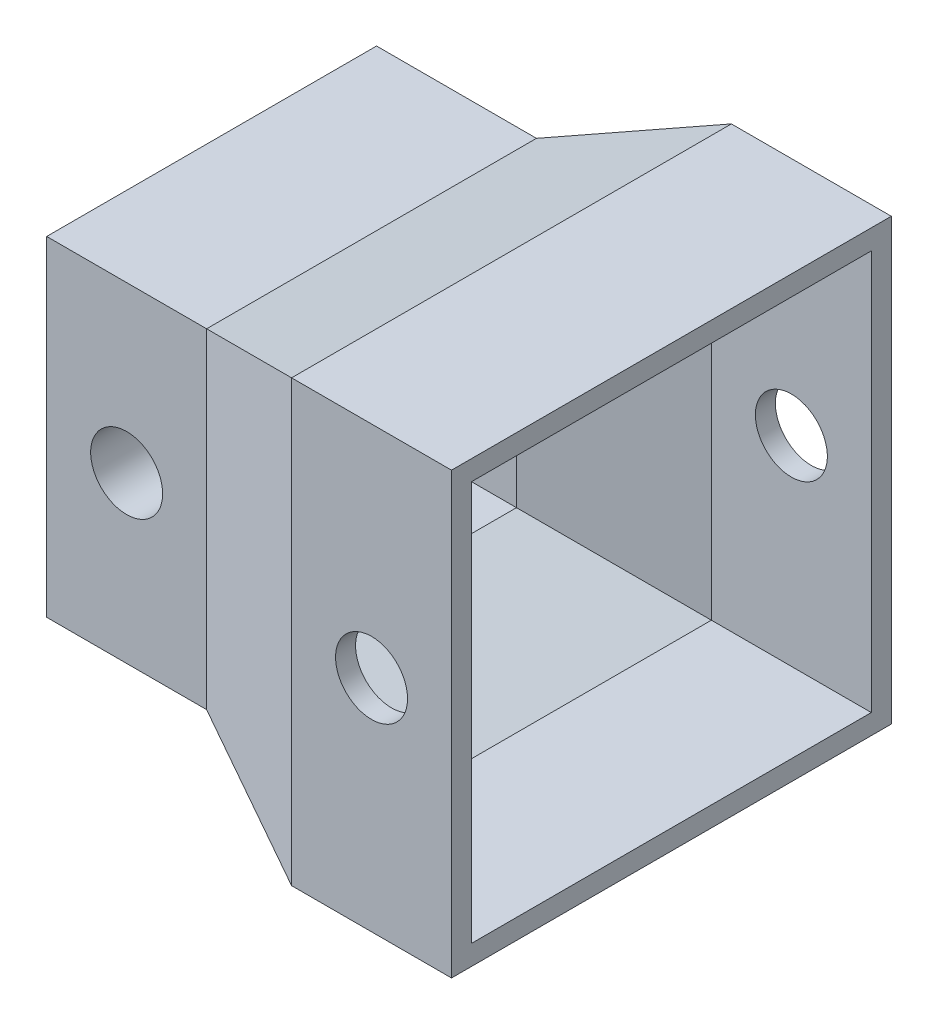
SolidWorks part; units mm, degrees
ref_plane "正面" through (0, 0, 0) normal (0, 0, 1) x (1, 0, 0)
ref_plane "平面" through (0, 0, 0) normal (0, 1, 0) x (1, 0, 0)
ref_plane "右側面" through (0, 0, 0) normal (1, 0, 0) x (0, 0, -1)
sketch "ｽｹｯﾁ1" plane through (0, 0, 0) normal (0, 0, 1) x (1, 0, 0)
  circle A0 centre (0, 0) radius 2.5
  dimension "D1" = 5
extrude "ﾎﾞｽ - 押し出し1" add sketch "ｽｹｯﾁ1" along normal blind 1.5
sketch "ｽｹｯﾁ2" plane through (0, 0, 1.5) normal (0, 0, 1) x (1, 0, 0)
  circle A0 centre (0, 0) radius 3.5
  dimension "D1" = 7
extrude "ﾎﾞｽ - 押し出し2" add sketch "ｽｹｯﾁ2" along normal blind 1
sketch "ｽｹｯﾁ3" plane through (0, 0, 2.5) normal (0, 0, 1) x (1, 0, 0)
  circle A0 centre (0, 0) radius 2.5 construction
  circle A1 centre (0, 0) radius 2.5
extrude "ﾎﾞｽ - 押し出し3" add sketch "ｽｹｯﾁ3" along normal blind 2.5
sketch "ｽｹｯﾁ4" plane through (0, 0, 5) normal (0, 0, 1) x (1, 0, 0)
  circle A1 centre (0, 0) radius 3.5
  circle A2 centre (0, 0) radius 3.5
  dimension "D1" = 0
extrude "ﾎﾞｽ - 押し出し4" add sketch "ｽｹｯﾁ4" along normal blind 1
sketch "ｽｹｯﾁ5" plane through (0, 0, 6) normal (0, 0, 1) x (1, 0, 0)
  circle A0 centre (0, 0) radius 2.5 construction
  circle A1 centre (0, 0) radius 2.5
extrude "ﾎﾞｽ - 押し出し5" add sketch "ｽｹｯﾁ5" along normal blind 2.5
sketch "ｽｹｯﾁ6" plane through (0, 0, 8.5) normal (0, 0, 1) x (1, 0, 0)
  circle A1 centre (0, 0) radius 3.5
  circle A2 centre (0, 0) radius 3.5
  dimension "D1" = 0
extrude "ﾎﾞｽ - 押し出し6" add sketch "ｽｹｯﾁ6" along normal blind 1
sketch "ｽｹｯﾁ7" plane through (0, 0, 9.5) normal (0, 0, 1) x (1, 0, 0)
  circle A0 centre (0, 0) radius 2.5 construction
  circle A1 centre (0, 0) radius 2.5
extrude "ﾎﾞｽ - 押し出し7" add sketch "ｽｹｯﾁ7" along normal blind 2.5
sketch "ｽｹｯﾁ10" plane through (0, 0, 12) normal (0, 0, 1) x (1, 0, 0)
  circle A1 centre (0, 0) radius 3.5
  circle A2 centre (0, 0) radius 3.5
  dimension "D1" = 0
extrude "ﾎﾞｽ - 押し出し9" add sketch "ｽｹｯﾁ10" along normal blind 1
sketch "ｽｹｯﾁ11" plane through (0, 0, 13) normal (0, 0, 1) x (1, 0, 0)
  circle A0 centre (0, 0) radius 2.5 construction
  circle A1 centre (0, 0) radius 2.5
extrude "ﾎﾞｽ - 押し出し10" add sketch "ｽｹｯﾁ11" along normal blind 1.5
sketch "ｽｹｯﾁ12" plane through (0, 0, 14.5) normal (0, 0, 1) x (1, 0, 0)
  circle A0 centre (0, 0) radius 1.8
  dimension "D1" = 3.6
extrude "ｶｯﾄ - 押し出し2" cut sketch "ｽｹｯﾁ12" against normal through all
ref_plane "平面1" through (15, 0, 0) normal (1, 0, 0) x (0, 0, -1)
sketch "ｽｹｯﾁ13" plane through (15, 0, 0) normal (1, 0, 0) x (0, 0, -1)
  line L0 (0, 0) -> (-7.25, 0) construction
  line L1 (-18.25, -11) -> (3.75, -11)
  line L2 (-18.25, -11) -> (-18.25, 11)
  line L3 (-18.25, 11) -> (3.75, 11)
  line L4 (3.75, -11) -> (3.75, 11)
  line L5 (-18.25, -11) -> (3.75, 11) construction
  line L6 (-18.25, 11) -> (3.75, -11) construction
  line L7 (-7.25, 0) -> (-14.5, 0) construction
  line L8 (-14.5, 2.5) -> (-14.5, -2.5) construction
  line L10 (2.75, -10) -> (-17.25, -10)
  line L11 (2.75, -10) -> (2.75, 10)
  line L12 (2.75, 10) -> (-17.25, 10)
  line L13 (-17.25, -10) -> (-17.25, 10)
  line L14 (2.75, -10) -> (-17.25, 10) construction
  line L15 (2.75, 10) -> (-17.25, -10) construction
  point P4 (-7.25, 0)
  dimension "D1" = 22
  dimension "D2" = 22
  dimension "D3" = 1
extrude "ﾎﾞｽ - 押し出し11" add sketch "ｽｹｯﾁ13" along normal blind 4 and the other way blind 4 separate body
sketch "ｽｹｯﾁ14" plane through (0, 0, 0) normal (1, 0, 0) x (0, 0, -1)
  line L0 (-18.25, 11) -> (3.75, -11) construction
  line L1 (1, -8.25) -> (-15.5, -8.25)
  line L2 (1, -8.25) -> (1, 8.25)
  line L3 (1, 8.25) -> (-15.5, 8.25)
  line L4 (-15.5, -8.25) -> (-15.5, 8.25)
  line L5 (1, -8.25) -> (-15.5, 8.25) construction
  line L6 (1, 8.25) -> (-15.5, -8.25) construction
  line L7 (-14.5, 2.5) -> (-14.5, -2.5) construction
  line L8 (0, -7.25) -> (-14.5, -7.25)
  line L9 (0, -7.25) -> (0, 7.25)
  line L10 (0, 7.25) -> (-14.5, 7.25)
  line L11 (-14.5, -7.25) -> (-14.5, 7.25)
  line L12 (0, -7.25) -> (-14.5, 7.25) construction
  line L13 (0, 7.25) -> (-14.5, -7.25) construction
  point P0 (-7.25, 0)
  point P9 (-7.25, 0)
  dimension "D1" = 1
extrude "ﾎﾞｽ - 押し出し12" add sketch "ｽｹｯﾁ14" along normal blind 4 and the other way blind 4
sketch "ｽｹｯﾁ16" plane through (11, 0, 0) normal (-1, 0, 0) x (0, 0, 1)
  line L0 (-3.75, 11) -> (-2.75, 10)
  line L1 (-2.75, 10) -> (17.25, 10)
  line L2 (17.25, 10) -> (18.25, 11)
  line L3 (18.25, 11) -> (-3.75, 11)
sketch "ｽｹｯﾁ17" plane through (4, 0, 0) normal (1, 0, 0) x (0, 0, -1)
  line L0 (-15.5, 8.25) -> (-14.5, 7.25)
  line L1 (-14.5, 7.25) -> (0, 7.25)
  line L2 (0, 7.25) -> (1, 8.25)
  line L3 (1, 8.25) -> (-15.5, 8.25)
loft "ﾛﾌﾄ2" add profiles "ｽｹｯﾁ16", "ｽｹｯﾁ17" connector at (11, 10, -2.75) connector at (4, 7.25, 0)
sketch "ｽｹｯﾁ18" plane through (0, 0, 0) normal (0, 1, 0) x (1, 0, 0)
  line L0 (0, 1) -> (0, -15.5)
  line L1 (-4, 1) -> (4, 1) construction
  line L2 (-4, -15.5) -> (4, -15.5) construction
  line L3 (0, -7.25) -> (-10, -7.25)
  dimension "D1" = 10
pattern_circular "円形ﾊﾟﾀｰﾝ1" count 4 over 360 about axis through (0, 0, 7.25) along (-1, 0, 0) of "ﾛﾌﾄ2" reverse direction yes
sketch "ｽｹｯﾁ19" plane through (0, 0, 15.5) normal (0, 0, 1) x (1, 0, 0)
  circle A1 centre (0, 0) radius 1.8
  circle A2 centre (0, 0) radius 1.8
  dimension "D1" = 0
extrude "ｶｯﾄ - 押し出し3" cut sketch "ｽｹｯﾁ19" against normal through all
sketch "ｽｹｯﾁ20" plane through (0, 0, 18.25) normal (0, 0, 1) x (1, 0, 0)
  line L0 (15, -12.1001) -> (15, 12.1001) construction
  line L1 (0, 0) -> (15, 0) construction
  circle A0 centre (15, 0) radius 1.8
  dimension "D1" = 3.6
extrude "ｶｯﾄ - 押し出し4" cut sketch "ｽｹｯﾁ20" against normal through all
